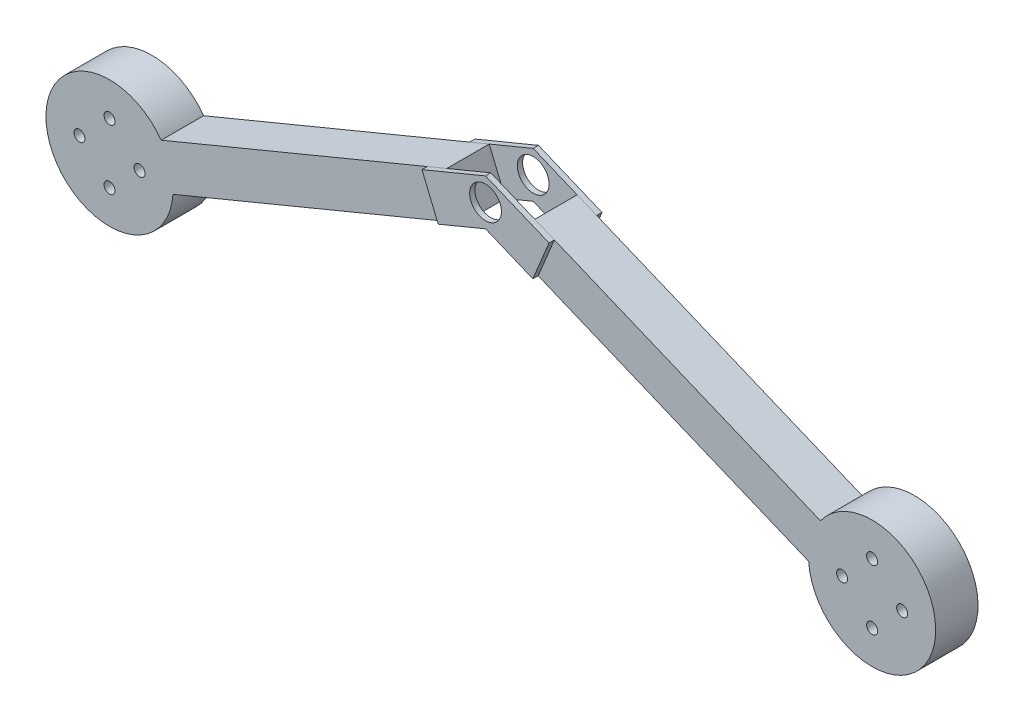
SolidWorks part; units mm, degrees
ref_plane "Front Plane" through (0, 0, 0) normal (0, 0, 1) x (1, 0, 0)
ref_plane "Top Plane" through (0, 0, 0) normal (0, 1, 0) x (1, 0, 0)
ref_plane "Right Plane" through (0, 0, 0) normal (1, 0, 0) x (0, 0, -1)
sketch "Sketch1" plane through (0, 0, 0) normal (0, 0, 1) x (1, 0, 0)
  line L0 (-216.5317, -101.2616) -> (-26.3667, -22.4927)
  line L1 (-216.5317, -101.2616) -> (-206.8115, -124.7281)
  line L2 (-26.3667, -22.4927) -> (-16.6466, -45.9592)
  line L3 (-206.8115, -124.7281) -> (-16.6466, -45.9592)
  line L4 (26.3667, -22.4927) -> (216.5317, -101.2616)
  line L5 (26.3667, -22.4927) -> (16.6466, -45.9592)
  line L6 (216.5317, -101.2616) -> (206.8115, -124.7281)
  line L7 (16.6466, -45.9592) -> (206.8115, -124.7281)
  line L8 (-26.3667, -22.4927) -> (0, -11.5712)
  line L9 (0, -11.5712) -> (26.3667, -22.4927)
  line L10 (0, 19.4566) -> (0, -8.1997) construction
  line L11 (-228.6, -115.5981) -> (-228.6, -77.4981) construction
  line L12 (228.6, -115.5981) -> (228.6, -77.4981) construction
  line L13 (-38.1, -27.3527) -> (-28.3798, -50.8193)
  line L14 (28.3798, -50.8193) -> (38.1, -27.3527)
  line L15 (-28.3798, -50.8193) -> (0, -39.064)
  line L16 (0, -39.064) -> (28.3798, -50.8193)
  line L17 (0, -25.3176) -> (-16.2838, -25.3176) construction
  circle A0 centre (-228.6, -115.5981) radius 38.1
  circle A3 centre (-228.6, -115.5981) radius 85.471 construction
  circle A4 centre (228.6, -115.5981) radius 38.1
  circle A5 centre (228.6, -115.5981) radius 85.471 construction
  circle A6 centre (0, -25.3176) radius 9.525
  point P16 (-228.6, -97.5981)
  point P17 (228.6, -97.5981)
  dimension "D5" = 76.2
  dimension "D6" = 170.942
  dimension "D9" = 19.05
  dimension "D1" = 135
  dimension "D2" = 25.4
  dimension "D3" = 25.4
  dimension "D4" = 18
  dimension "D7" = 18
  dimension "D8" = 457.2
  dimension "D10" = 12.7
  dimension "D11" = 76.2
extrude "Boss-Extrude1" add sketch "Sketch1" along normal blind 25.4 contours L0 A0 L3 L1 | L3 A0 L0 L1 | A0 L3 L2 L0 | A4 L4 L5 L7 | L4 A4 L7 L6 | L7 A4 L4 L6 | L0 L13 L3 L2 | L7 L14 L4 L5 region at (-112.969, -72.1484, 0) region at (-27.3733, -36.656, 0) region at (-202.2821, -108.7895, 0) region at (-231.995, -116.4764, 0) region at (27.3733, -36.656, 0) region at (112.969, -72.1484, 0) region at (231.995, -116.4764, 0) region at (202.2821, -108.7895, 0)
hole_wizard "M6 Clearance Hole1" positions "3DSketch2" profile "Sketch3" hole size "M6" standard "ANSI Metric" end condition through all
sketch3d "3DSketch2"
  point P2 (-228.6, -97.5981, 0)
sketch "Sketch3" plane through (-228.6, -97.5981, 0) normal (1, 0, 0) x (0, 1, 0)
  line L0 (0, 0) -> (0, 25.4)
  line L1 (0, 25.4) -> (3.3, 25.4)
  line L2 (3.3, 25.4) -> (3.3, 0)
  line L5 (3.3, 0) -> (0, 0)
  line L11 (0, -6.35) -> (0, 107.95) construction
  dimension "Thru Hole Dia." = 6.6
  dimension "Thru Hole Depth" = 25.4
pattern_circular "CirPattern1" count 4 over 360 about axis through (-228.6, -115.5981, 25.4) along (0, 0, -1) of "M6 Clearance Hole1"
mirror "Mirror3" about plane through (0, 0, 0) normal (1, 0, 0) of "CirPattern1"
extrude "Boss-Extrude2" add sketch "Sketch1<3>" against normal blind 3.175 separate body contours L0 L13 L3 L2 | L15 L16 L5 L9 L8 L2 | L7 L14 L4 L5 region at (-27.3733, -36.656, 0) region at (-12.9424, -17.6136, 0) region at (27.3733, -36.656, 0)
sketch "Sketch1<3>" plane through (0, 0, 0) normal (0, 0, 1) x (1, 0, 0) same geometry as "Sketch1"
extrude "Boss-Extrude3" add sketch "Sketch1<5>" along normal blind 3.175 from surface separate body contours L0 L13 L3 L2 | L15 L16 L5 L9 L8 L2 A6 | L7 L14 L4 L5 region at (-27.3733, -36.656, 0) region at (-12.9424, -17.6136, 0) region at (27.3733, -36.656, 0) starting at face at (-213.9, -115.5981, 25.4)
sketch "Sketch1<5>" plane through (0, 0, 0) normal (0, 0, 1) x (1, 0, 0) same geometry as "Sketch1"
equation "\"Rover_Length\"= 25in"
equation "\"Rover_Width\"= 18in"
equation "\"Rover_Height\"= 12in"
equation "\"Chassis_Wheelbase\"= 18in"
equation "\"Chassis_WheelDiam\"= 171mm"
equation "\"Chassis_ArmDiamWidth\"= 0.75in"
equation "\"Chassis_ArmAngle\"= 135deg"
equation "\"Chassis_HubMountOD\"= 3in"
equation "\"Chassis_WheelBoltHole\"= 36mm"
equation "\"Chassis_WheelBoltNum\"= 4"
equation "\"Chassis_DiffBarLength\"= 12in"
equation "\"Chassis_DiffBarWidth\"= 1in"
equation "\"Chassis_DiffBarHeight\"= 0.5in"
equation "\"Chassis_DiffLinkage_Length\"= 2.5in"
equation "\"D1@Sketch1\"=\"Chassis_ArmAngle\""
equation "\"D2@Sketch1\"=\"Chassis_DiffBarWidth\""
equation "\"D3@Sketch1\"=\"Chassis_DiffBarWidth\""
equation "\"D5@Sketch1\"=\"Chassis_HubMountOD\""
equation "\"D4@Sketch1\"=\"Chassis_WheelBoltHole\"/2"
equation "\"D7@Sketch1\"=\"Chassis_WheelBoltHole\"/2"
equation "\"D8@Sketch1\"=\"Chassis_Wheelbase\""
equation "\"D1@Boss-Extrude1\"=\"Chassis_DiffBarWidth\""
equation "\"Chassis_MountBracketThickness\"= 0.125in"
equation "\"Chassis_MountBracketWidth\"= 3in"
equation "\"Chassis_MountBacketOverlap\"= 0.5in"
equation "\"Chassis_ArmShaftDiam\"= 0.75in"
equation "\"D10@Sketch1\"=\"Chassis_MountBacketOverlap\""
equation "\"D11@Sketch1\"=\"Chassis_MountBracketWidth\""
equation "\"D9@Sketch1\"=\"Chassis_ArmShaftDiam\""
equation "\"D1@Boss-Extrude3\"=\"Chassis_MountBracketThickness\""
equation "\"D1@Boss-Extrude2\"=\"Chassis_MountBracketThickness\""
